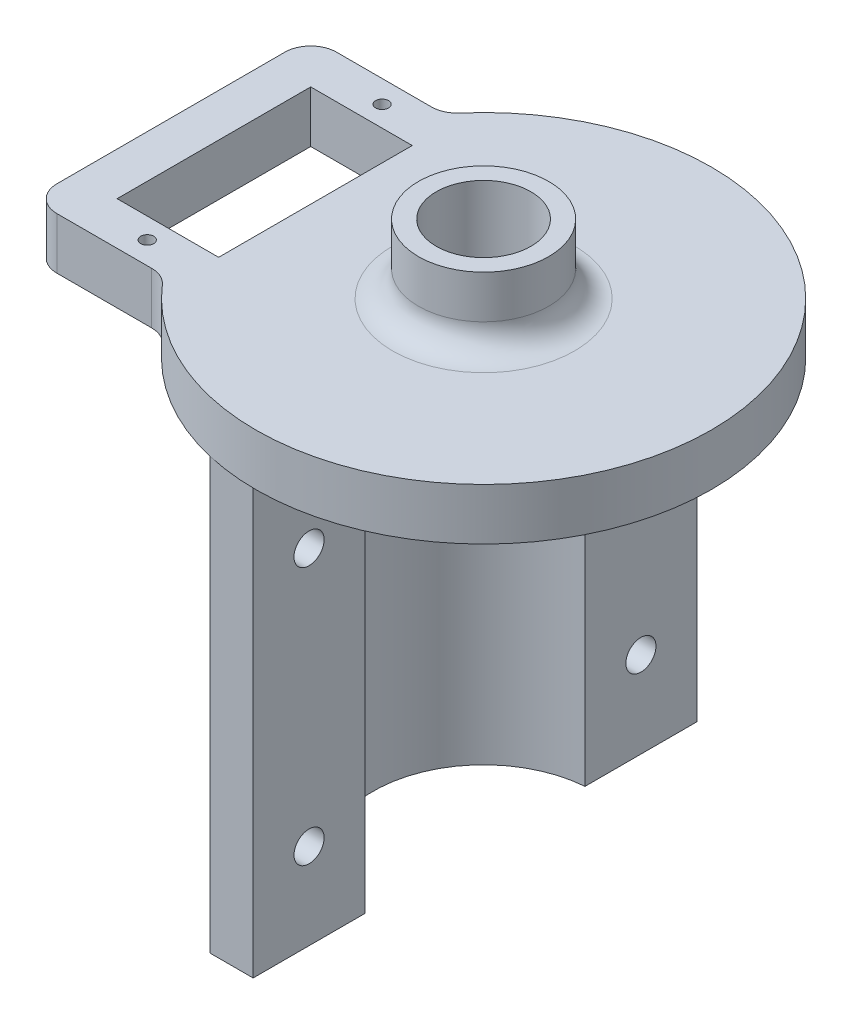
SolidWorks part; units mm, degrees
ref_plane "Front Plane" through (0, 0, 0) normal (0, 0, 1) x (1, 0, 0)
ref_plane "Top Plane" through (0, 0, 0) normal (0, 1, 0) x (1, 0, 0)
ref_plane "Right Plane" through (0, 0, 0) normal (1, 0, 0) x (0, 0, -1)
sketch "Sketch6" plane through (0, 0, 0) normal (0, -1, 0) x (1, 0, 0)
  line L5 (-1, 25.7848) -> (-1, 12.786)
  line L6 (-1, 25.7848) -> (-6, 25.7848)
  line L7 (-6, 25.7848) -> (-6, 16.7848)
  line L8 (-6, -16.7848) -> (-6, -25.7848)
  line L9 (-6, -25.7848) -> (-1, -25.7848)
  line L10 (-1, -25.7848) -> (-1, -12.786)
  line L11 (-12.825, 0) -> (-17.825, 0) construction
  arc A0 (-1, 12.786) -> (-1, -12.786) centre (0, 0) ccw
  arc A1 (-6, 16.7848) -> (-6, -16.7848) centre (0, 0) ccw
  dimension "D1" = 25.65
  dimension "D2" = 5
  dimension "D3" = 1
  dimension "D4" = 9
extrude "Boss-Extrude4" add sketch "Sketch6" along normal blind 50
sketch "Sketch7" plane through (-1, 0, 0) normal (1, 0, 0) x (0, 0, -1)
  line L0 (-19.2854, -50) -> (-19.2854, 0) construction
  line L3 (0, 0) -> (0, -50) construction
  line L6 (-25.7848, -25) -> (25.7848, -25) construction
  line L11 (-12.786, 0) -> (-25.7848, 0) construction
  line L12 (-12.786, -50) -> (-25.7848, -50) construction
  line L13 (-25.7848, -50) -> (-25.7848, 0) construction
  line L14 (25.7848, -50) -> (25.7848, 0) construction
  line L15 (-12.786, -50) -> (12.786, -50) construction
  circle A0 centre (-19.2854, -10) radius 1.75
  circle A1 centre (-19.2854, -40) radius 1.75
  circle A2 centre (19.2854, -40) radius 1.75
  circle A3 centre (19.2854, -10) radius 1.75
  dimension "D1" = 10
  dimension "D2" = 3.5
extrude "Cut-Extrude1" cut sketch "Sketch7" against normal through all
sketch "Sketch8" plane through (0, 0, 0) normal (0, 1, 0) x (1, 0, 0)
  line L0 (-25.4436, -13.65) -> (-25.4436, 13.65) construction
  line L1 (-31.3436, -11.25) -> (-19.5436, -11.25)
  line L2 (-31.3436, -11.25) -> (-31.3436, 11.25)
  line L3 (-31.3436, 11.25) -> (-19.5436, 11.25)
  line L4 (-19.5436, -11.25) -> (-19.5436, 11.25)
  line L5 (-33.3436, -16.25) -> (-22.319, -16.25)
  line L6 (-36.3436, -13.25) -> (-36.3436, 13.25)
  line L7 (-33.3436, 16.25) -> (-22.319, 16.25)
  circle A1 centre (-25.4436, 13.65) radius 0.75
  circle A2 centre (-25.4436, -13.65) radius 0.75
  arc A3 (-20.0472, -17.2906) -> (-20.0472, 17.2906) centre (0, 0) ccw
  arc A4 (-33.3436, -16.25) -> (-36.3436, -13.25) centre (-33.3436, -13.25) cw
  arc A5 (-36.3436, 13.25) -> (-33.3436, 16.25) centre (-33.3436, 13.25) cw
  arc A6 (-22.319, 16.25) -> (-20.0472, 17.2906) centre (-22.319, 19.25) ccw
  arc A7 (-22.319, -16.25) -> (-20.0472, -17.2906) centre (-22.319, -19.25) cw
  circle A8 centre (-25.4436, 5.35) radius 5.9 construction
  point P7 (-19.5436, 0)
  point P13 (-25.4436, -11.25)
  point P18 (-25.4436, 0)
  point P24 (-36.3436, 0)
  dimension "D1" = 5
  dimension "D4" = 1.5
  dimension "D7" = 5
  dimension "D8" = 3
  dimension "D9" = 3
  dimension "D10" = 11.8
  dimension "D2" = 11.8
  dimension "D3" = 22.5
  dimension "D5" = 27.3
  dimension "D6" = 26
extrude "Boss-Extrude5" add sketch "Sketch8" along normal blind 6
sketch "Sketch9" plane through (0, 6, 0) normal (0, 1, 0) x (1, 0, 0)
  circle A0 centre (0, 0) radius 7.57
  dimension "D1" = 15.14
extrude "Boss-Extrude6" add sketch "Sketch9" along normal blind 8
fillet "Fillet1" radius 3 1 edges at (0, 6, 7.57)
sketch "Sketch10" plane through (0, 14, 0) normal (0, 1, 0) x (1, 0, 0)
  circle A0 centre (0, 0) radius 5.5
  dimension "D1" = 11
extrude "Cut-Extrude2" cut sketch "Sketch10" against normal through all
